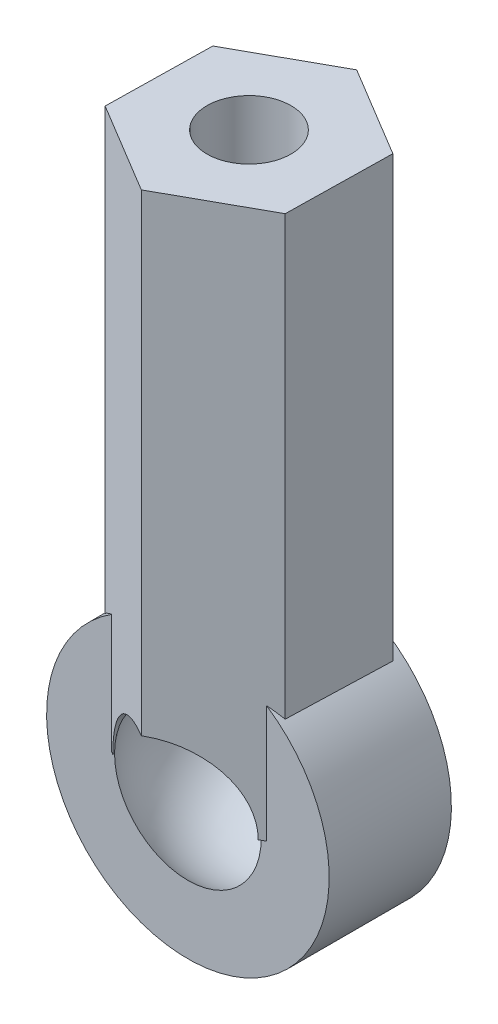
SolidWorks part; units mm, degrees
ref_plane "前基準面" through (0, 0, 0) normal (0, 0, 1) x (1, 0, 0)
ref_plane "上基準面" through (0, 0, 0) normal (0, 1, 0) x (1, 0, 0)
ref_plane "右基準面" through (0, 0, 0) normal (1, 0, 0) x (0, 0, -1)
sketch "草圖1" plane through (0, 0, 0) normal (0, 0, 1) x (1, 0, 0)
  circle A0 centre (0, 0) radius 3.7
  dimension "D1" = 7.4
extrude "填料-伸長1" add sketch "草圖1" along normal blind 1.6 and the other way blind 1.6
sketch "草圖8" plane through (0, 0, 0) normal (0, 1, 0) x (1, 0, 0)
  line L1 (0.0487, 2.7709) -> (-2.3753, 1.4276)
  line L2 (-2.3753, 1.4276) -> (-2.424, -1.3433)
  line L3 (-2.424, -1.3433) -> (-0.0487, -2.7709)
  line L4 (-0.0487, -2.7709) -> (2.3753, -1.4276)
  line L5 (2.3753, -1.4276) -> (2.424, 1.3433)
  line L6 (2.424, 1.3433) -> (0.0487, 2.7709)
  circle A1 centre (0, 0) radius 2.4 construction
  dimension "D1" = 4.8
extrude "填料-伸長3" add sketch "草圖8" along normal blind 14.3
sketch "草圖7" plane through (0, 0, 0) normal (0, 0, 1) x (1, 0, 0)
  line L0 (0, 2.5) -> (0, -2.5) construction
  line L1 (0, 2.5) -> (0, -2.5)
  arc A0 (0, -2.5) -> (0, 2.5) centre (0, 0) ccw
  dimension "D1" = 5
revolve "除料-旋轉7" cut sketch "草圖7" angle 360 about L0
sketch "草圖9" plane through (0, 14.3, 0) normal (0, 1, 0) x (1, 0, 0)
  circle A0 centre (0, 0) radius 1.1
  dimension "D1" = 2.2
extrude "除料-伸長1" cut sketch "草圖9" against normal blind 5
sketch "草圖10" plane through (0, 0, -1.6) normal (0, 0, -1) x (-1, 0, 0)
  circle A0 centre (0, 0) radius 1.9209
extrude "除料-伸長2" cut sketch "草圖10" against normal through all and the other way through all
